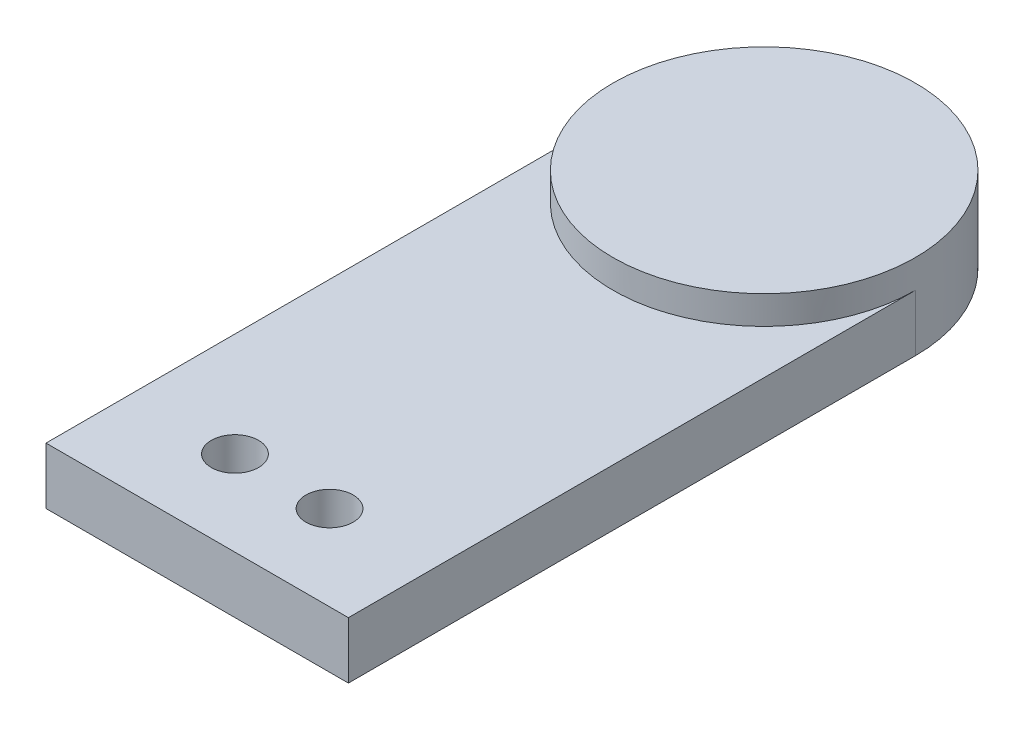
SolidWorks part; units mm, degrees
ref_plane "Plano frontal" through (0, 0, 0) normal (0, 0, 1) x (1, 0, 0)
ref_plane "Plano superior" through (0, 0, 0) normal (0, 1, 0) x (1, 0, 0)
ref_plane "Plano direito" through (0, 0, 0) normal (1, 0, 0) x (0, 0, -1)
sketch "Sketch1" plane through (0, 0, 0) normal (0, 1, 0) x (1, 0, 0)
  circle A0 centre (0, 0) radius 8
  dimension "D1" = 16
extrude "Boss-Extrude1" add sketch "Sketch1" against normal blind 1.5 and the other way blind 3
sketch "Sketch2" plane through (0, 0, 0) normal (0, 1, 0) x (1, 0, 0)
  line L1 (-8, 0) -> (8, 0)
  line L2 (-8, 0) -> (-8, -30)
  line L3 (-8, -30) -> (8, -30)
  line L4 (8, 0) -> (8, -30)
  circle A1 centre (0, 0) radius 8 construction
  dimension "D1" = 30
extrude "Boss-Extrude2" add sketch "Sketch2" along normal mid plane 3
sketch "Sketch3" plane through (0, -1.5, 0) normal (0, -1, 0) x (-1, 0, 0)
  line L1 (8, -30) -> (-8, -30) construction
  circle A0 centre (2.5031, -25.5) radius 1.25
  circle A1 centre (-2.5031, -25.5) radius 1.25
  dimension "D4" = 2.5
  dimension "D5" = 2.5
  dimension "D1" = 2.5031
  dimension "D2" = 2.5031
  dimension "D3" = 4.5
extrude "Cut-Extrude1" cut sketch "Sketch3" against normal up to next
sketch "Sketch4" plane through (0, -1.5, 0) normal (0, -1, 0) x (-1, 0, 0)
  line L0 (-3.3, 0) -> (3.3, 0)
  circle A0 centre (0, 0) radius 3.3
  dimension "D1" = 6.6
revolve "Cut-Revolve21" cut sketch "Sketch4" angle 360 about L0 region at (0, -1.5, 1.4006)
equation "\"D2@Sketch3\"=\"D1@Sketch3\""
equation "\"D5@Sketch3\"=\"D4@Sketch3\""
